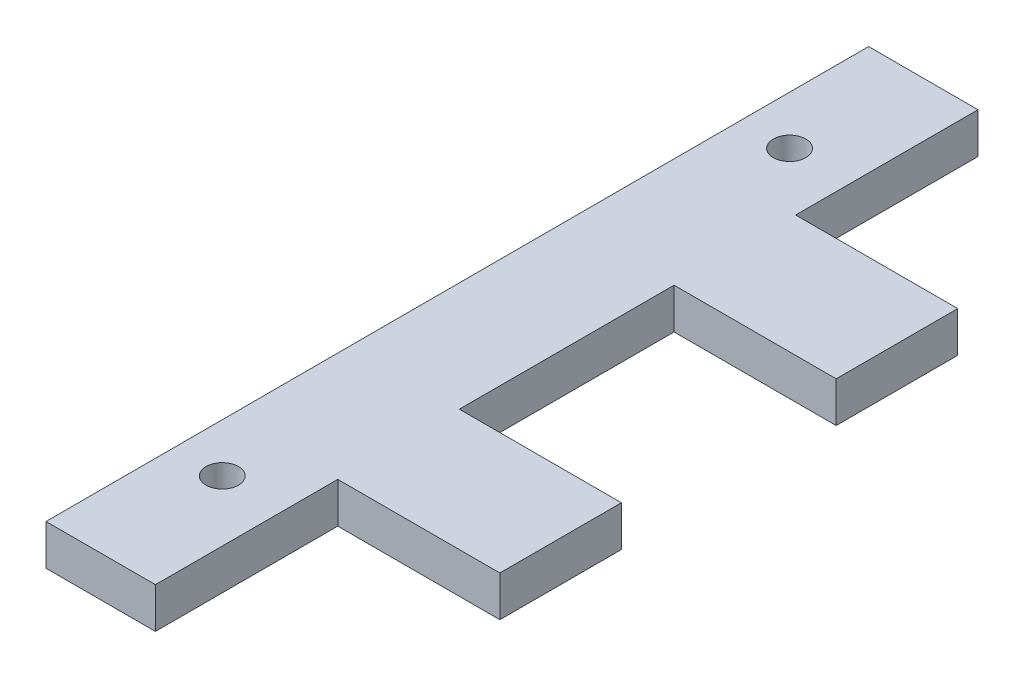
SolidWorks part; units mm, degrees
ref_plane "Front" through (0, 0, 0) normal (0, 0, 1) x (1, 0, 0)
ref_plane "Top" through (0, 0, 0) normal (0, 1, 0) x (1, 0, 0)
ref_plane "Right" through (0, 0, 0) normal (1, 0, 0) x (0, 0, -1)
sketch "Эскиз1" plane through (0, 0, 0) normal (0, 1, 0) x (1, 0, 0)
  line L1 (0, 0) -> (2.7, 0)
  line L2 (0, 0) -> (0, -20.3)
  line L3 (0, -20.3) -> (2.7, -20.3)
  line L4 (2.7, 0) -> (2.7, -20.3)
  line L5 (2.7, -4.5) -> (6.7, -4.5)
  line L6 (2.7, -4.5) -> (2.7, -7.5)
  line L7 (2.7, -7.5) -> (6.7, -7.5)
  line L8 (6.7, -4.5) -> (6.7, -7.5)
  line L9 (2.7, -12.8) -> (6.7, -12.8)
  line L10 (2.7, -12.8) -> (2.7, -15.8)
  line L11 (2.7, -15.8) -> (6.7, -15.8)
  line L12 (6.7, -12.8) -> (6.7, -15.8)
  circle A0 centre (1.2, -3.15) radius 0.4
  circle A1 centre (1.2, -17.15) radius 0.4
  dimension "D9" = 0.8
  dimension "D10" = 0.8
  dimension "D1" = 2.7
  dimension "D2" = 20.3
  dimension "D3" = 3
  dimension "D4" = 3
  dimension "D5" = 4
  dimension "D6" = 4
  dimension "D7" = 4.5
  dimension "D8" = 4.5
  dimension "D11" = 3.15
  dimension "D12" = 3.15
  dimension "D13" = 1.2
  dimension "D14" = 1.2
extrude "Бобышка-Вытянуть1" add sketch "Эскиз1" along normal blind 1 contours L4 L1 L2 L3 A1 A0 | L12 L9 L4 L11 | L8 L5 L4 L7 region at (1.3528, 0, 10.15) region at (4.7, 0, 6) region at (4.7, 0, 14.3)
